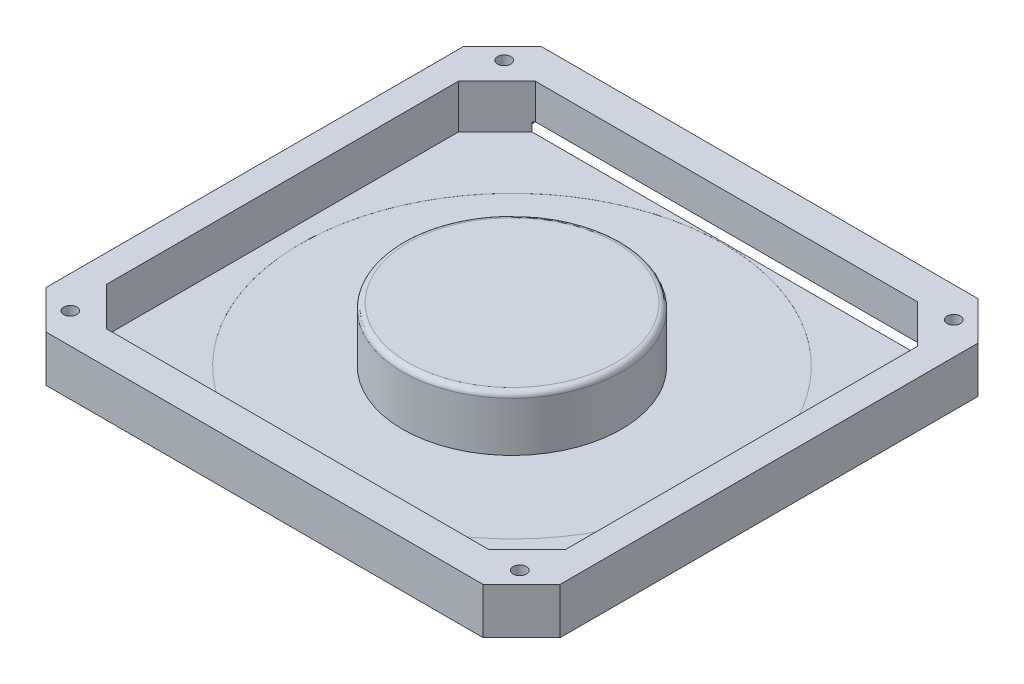
SolidWorks part; units mm, degrees
ref_plane "Front Plane" through (0, 0, 0) normal (0, 0, 1) x (1, 0, 0)
ref_plane "Top Plane" through (0, 0, 0) normal (0, 1, 0) x (1, 0, 0)
ref_plane "Right Plane" through (0, 0, 0) normal (1, 0, 0) x (0, 0, -1)
sketch "Sketch1" plane through (0, 0, 0) normal (0, 1, 0) x (1, 0, 0)
  line L0 (-49.3, 41.6048) -> (-43.2, 47.7048)
  line L1 (-34, -47.5952) -> (34, -47.5952)
  line L2 (-49.3, -37.9952) -> (-49.3, 41.6048)
  line L3 (-43.2, 47.7048) -> (-35.5, 47.7048)
  line L4 (49.3, -37.9952) -> (49.3, 41.6048)
  line L5 (-49.3, -47.5952) -> (49.2706, 47.5669) construction
  line L6 (-49.3548, 47.6481) -> (49.3, -47.5952) construction
  line L7 (0, 0) -> (0, 47.7048) construction
  line L8 (49.3, 41.6048) -> (43.2, 47.7048)
  line L9 (-46.8, -44.0952) -> (-46.8, -38.9952)
  line L10 (-45.8, -45.0952) -> (-35, -45.0952)
  line L11 (46.8, -44.0952) -> (46.8, -38.9952)
  line L12 (-49.3, -37.9952) -> (-47.8, -37.9952)
  line L13 (-34, -47.5952) -> (-34, -46.0952)
  line L14 (34, -47.5952) -> (34, -46.0952)
  line L15 (49.3, -37.9952) -> (47.8, -37.9952)
  line L16 (35, -45.0952) -> (45.8, -45.0952)
  line L17 (-46.8, -45.0952) -> (-46.8, 41.6048) construction
  line L18 (46.8, -45.0952) -> (46.8, 41.6048) construction
  line L19 (-34.5, 44.0048) -> (-4.5, 44.0048)
  line L20 (-46.8, -45.0952) -> (46.8, -45.0952) construction
  line L21 (-49.3, -47.5952) -> (49.3, -47.5952) construction
  line L22 (-49.3, -47.5952) -> (-49.3, 41.6048) construction
  line L23 (49.3, -47.5952) -> (49.3, 41.6048) construction
  line L24 (-35.5, 47.7048) -> (-35.5, 45.0048)
  line L25 (-3.5, 47.7048) -> (-3.5, 45.0048)
  line L26 (-3.5, 47.7048) -> (43.2, 47.7048)
  line L27 (-43.2, 44.0048) -> (43.2, 44.0048) construction
  line L28 (21.27, 40.7348) -> (23.81, 40.7348) construction
  line L29 (-43.2, 47.7048) -> (43.2, 47.7048) construction
  line L30 (28.67, 40.7348) -> (31.21, 40.7348) construction
  line L31 (28.67, 40.7348) -> (28.67, 43.2748) construction
  line L32 (28.67, 43.2748) -> (31.21, 43.2748) construction
  line L33 (31.21, 40.7348) -> (31.21, 43.2748) construction
  line L34 (28.67, 40.7348) -> (31.21, 43.2748) construction
  line L35 (28.67, 43.2748) -> (31.21, 40.7348) construction
  line L36 (21.27, 40.7348) -> (21.27, 43.2748) construction
  line L37 (21.27, 43.2748) -> (23.81, 43.2748) construction
  line L38 (23.81, 40.7348) -> (23.81, 43.2748) construction
  line L39 (21.27, 40.7348) -> (23.81, 43.2748) construction
  line L40 (21.27, 43.2748) -> (23.81, 40.7348) construction
  line L41 (13.87, 40.7348) -> (16.41, 40.7348) construction
  line L42 (13.87, 40.7348) -> (13.87, 43.2748) construction
  line L43 (13.87, 43.2748) -> (16.41, 43.2748) construction
  line L44 (16.41, 40.7348) -> (16.41, 43.2748) construction
  line L45 (13.87, 40.7348) -> (16.41, 43.2748) construction
  line L46 (13.87, 43.2748) -> (16.41, 40.7348) construction
  arc A0 (47.8, -37.9952) -> (46.8, -38.9952) centre (47.8, -38.9952) ccw
  arc A1 (35, -45.0952) -> (34, -46.0952) centre (35, -46.0952) ccw
  arc A2 (-34, -46.0952) -> (-35, -45.0952) centre (-35, -46.0952) ccw
  arc A3 (-46.8, -38.9952) -> (-47.8, -37.9952) centre (-47.8, -38.9952) ccw
  arc A4 (46.8, -44.0952) -> (45.8, -45.0952) centre (45.8, -44.0952) cw
  arc A5 (-45.8, -45.0952) -> (-46.8, -44.0952) centre (-45.8, -44.0952) cw
  arc A6 (-4.5, 44.0048) -> (-3.5, 45.0048) centre (-4.5, 45.0048) ccw
  arc A7 (-34.5, 44.0048) -> (-35.5, 45.0048) centre (-34.5, 45.0048) cw
  circle A8 centre (-33.77, 39.7448) radius 0.4
  circle A9 centre (-5.22, 39.7448) radius 0.4
  circle A10 centre (29.94, 42.0048) radius 0.2125
  circle A11 centre (28.67, 43.2748) radius 0.2125
  circle A12 centre (31.21, 43.2748) radius 0.2125
  circle A13 centre (31.21, 40.7348) radius 0.2125
  circle A14 centre (28.67, 40.7348) radius 0.2125
  circle A15 centre (22.54, 42.0048) radius 0.2125
  circle A16 centre (21.27, 43.2748) radius 0.2125
  circle A17 centre (23.81, 43.2748) radius 0.2125
  circle A18 centre (23.81, 40.7348) radius 0.2125
  circle A19 centre (21.27, 40.7348) radius 0.2125
  circle A20 centre (15.14, 42.0048) radius 0.2125
  circle A21 centre (13.87, 43.2748) radius 0.2125
  circle A22 centre (16.41, 43.2748) radius 0.2125
  circle A23 centre (16.41, 40.7348) radius 0.2125
  circle A24 centre (13.87, 40.7348) radius 0.2125
  point P0 (0, 0)
  point P26 (46.8, -37.9952)
  point P29 (34, -45.0952)
  point P32 (-34, -45.0952)
  point P35 (-46.8, -37.9952)
  dimension "D9" = 1
  dimension "D10" = 1
  dimension "D11" = 3.7
  dimension "D14" = 1
  dimension "D16" = 0.8
  dimension "D18" = 7.96
  dimension "D19" = 9.43
  dimension "D20" = 28.55
  dimension "D21" = 0.425
  dimension "D22" = 1.27
  dimension "D1" = 47.7048
  dimension "D2" = 98.6
  dimension "D3" = 6.1
  dimension "D4" = 6.1
  dimension "D5" = 95.3
  dimension "D6" = 2.5
  dimension "D7" = 85.7
  dimension "D8" = 15.3
  dimension "D12" = 13.8
  dimension "D13" = 32
  dimension "D15" = 137.1279
  dimension "D17" = 7.96
  dimension "D23" = 5.7
  dimension "D24" = 13.26
  dimension "D25" = 1.27
  dimension "D27" = 5.7
  dimension "D28" = 7.4
  dimension "D26" = 3
sketch "Sketch4" plane through (0, 0, 0) normal (0, 1, 0) x (1, 0, 0)
  line L0 (-46.75, 38) -> (-39.75, 45)
  line L1 (-39.75, -45) -> (39.75, -45)
  line L2 (-46.75, -38) -> (-46.75, 38)
  line L3 (-39.75, 45) -> (39.75, 45)
  line L4 (46.75, -38) -> (46.75, 38)
  line L5 (-46.75, -45) -> (46.75, 45) construction
  line L6 (-46.75, 45) -> (46.75, -45) construction
  line L7 (39.75, 45) -> (46.75, 38)
  line L8 (-39.75, -45) -> (-46.75, -38)
  line L9 (39.75, -45) -> (46.75, -38)
  point P0 (0, 0)
  dimension "D1" = 93.5
  dimension "D2" = 90
extrude "Boss-Extrude1" add sketch "Sketch4" along normal blind 8.4
sketch "Sketch5" plane through (0, 0, 0) normal (0, -1, 0) x (1, 0, 0)
  line L0 (36.75, -45) -> (36.75, -39.7048)
  line L1 (39.75, -45) -> (-39.75, -45) construction
  line L2 (35.75, -38.7048) -> (-35.75, -38.7048)
  line L3 (-36.75, -39.7048) -> (-36.75, -45)
  line L5 (46.75, 38) -> (46.75, -38) construction
  line L7 (-46.75, -38) -> (-46.75, 38) construction
  line L9 (-3.5, -47.7048) -> (43.2, -47.7048) construction
  arc A0 (-36.75, -39.7048) -> (-35.75, -38.7048) centre (-35.75, -39.7048) cw
  arc A1 (35.75, -38.7048) -> (36.75, -39.7048) centre (35.75, -39.7048) cw
  dimension "D4" = 1
  dimension "D1" = 10
  dimension "D2" = 10
  dimension "D3" = 9
extrude "Cut-Extrude1" cut sketch "Sketch5" against normal blind 2 and the other way through all
sketch "Sketch6" plane through (0, 8.4, 0) normal (0, 1, 0) x (1, 0, 0)
  line L0 (-41.75, 32) -> (-34.75, 39)
  line L1 (-34.75, -39) -> (34.75, -39)
  line L2 (-41.75, -32) -> (-41.75, 32)
  line L3 (-34.75, 39) -> (34.75, 39)
  line L4 (41.75, -32) -> (41.75, 32)
  line L5 (-41.75, -39) -> (41.75, 39) construction
  line L6 (-41.75, 39) -> (41.75, -39) construction
  line L7 (34.75, 39) -> (41.75, 32)
  line L8 (34.75, -39) -> (41.75, -32)
  line L9 (-41.75, -32) -> (-34.75, -39)
  point P0 (0, 0)
  dimension "D1" = 78
  dimension "D2" = 83.5
extrude "Cut-Extrude2" cut sketch "Sketch6" against normal blind 8
sketch "Sketch8" plane through (0, 0.4, 0) normal (0, 1, 0) x (1, 0, 0)
  circle A0 centre (0, 0) radius 38.5 construction
  circle A1 centre (0, 0) radius 19.9
  dimension "D1" = 77
  dimension "D2" = 39.8
extrude "Boss-Extrude2" add sketch "Sketch8" along normal blind 10
fillet "Fillet1" radius 1 1 edges at (0, 10.4, 19.9) type face fillet first side face at (0, 10.4, 19.9) second side face at (0, 10.4, 19.9)
sketch "Sketch9" plane through (0, 0.4, 0) normal (0, 1, 0) x (1, 0, 0)
  circle A0 centre (0, 0) radius 38.5
  dimension "D1" = 77
extrude "Cut-Extrude4" cut sketch "Sketch9" against normal blind 0.01
hole_wizard "M2 Clearance Hole1" positions "Sketch12" profile "Sketch10" hole size "M2" standard "ANSI Metric"
sketch "Sketch12" plane through (0, 8.4, 0) normal (0, 1, 0) x (1, 0, 0)
  line L0 (-49.3548, 47.6481) -> (49.3, -47.5952) construction
  line L1 (-49.3, -47.5952) -> (49.2706, 47.5669) construction
  point P0 (40.8712, -39.4579)
  point P4 (-40.8712, -39.4579)
  point P8 (-40.8712, 39.4579)
  point P10 (40.8712, 39.4579)
  dimension "D1" = 56.81
  dimension "D2" = 56.81
  dimension "D3" = 56.81
  dimension "D4" = 56.81
sketch "Sketch10" plane through (40.8712, 8.4, 39.4579) normal (1, 0, 0) x (0, 0, 1)
  line L0 (0, 0) -> (0, 38.821)
  line L1 (0, 38.821) -> (1.2, 38.1)
  line L2 (1.2, 38.1) -> (1.2, 0)
  line L5 (1.2, 0) -> (0, 0)
  line L10 (0, 38.821) -> (-1.2, 38.1) construction
  line L11 (0, -6.35) -> (0, 107.95) construction
  dimension "Hole Dia." = 2.4
  dimension "Hole Depth" = 38.1
  dimension "Drill Angle" = 118
